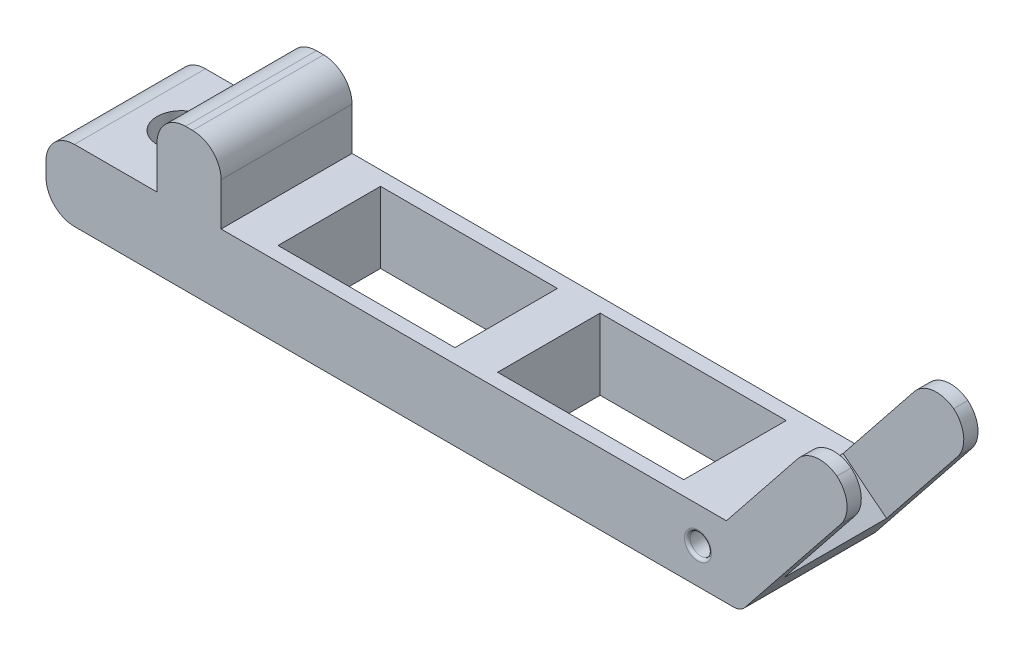
SolidWorks part; units mm, degrees
ref_plane "Front Plane" through (0, 0, 0) normal (0, 0, 1) x (1, 0, 0)
ref_plane "Top Plane" through (0, 0, 0) normal (0, 1, 0) x (1, 0, 0)
ref_plane "Right Plane" through (0, 0, 0) normal (1, 0, 0) x (0, 0, -1)
sketch "Szkic1" plane through (0, 0, 0) normal (0, 0, 1) x (1, 0, 0)
  line L6 (-27646.5587, -28.9023) -> (-27646.5587, -33.9023)
  line L7 (-27646.5587, -33.9023) -> (-27597.7587, -33.9023)
  line L8 (-27597.7587, -33.9023) -> (-27589.4735, -23.5176)
  line L9 (-27589.4735, -23.5176) -> (-27592.5221, -21.0854)
  line L10 (-27592.5221, -21.0854) -> (-27598.7587, -28.9023)
  line L11 (-27598.7587, -28.9023) -> (-27634.2587, -28.9023)
  line L12 (-27638.7587, -28.9023) -> (-27638.7587, -23.9023)
  line L13 (-27638.7587, -23.9023) -> (-27634.2587, -23.9023)
  line L14 (-27634.2587, -23.9023) -> (-27634.2587, -28.9023)
  line L15 (-27638.7587, -28.9023) -> (-27646.5587, -28.9023)
  line L16 (-27600.7587, -28.9023) -> (-27600.7587, -33.9023) construction
  circle A0 centre (-27600.7587, -31.4023) radius 0.75
  point P12 (-27600.7587, -31.4023)
  dimension "D9" = 1.5
  dimension "D1" = 3.9
  dimension "D2" = 47.8
  dimension "D3" = 10
  dimension "D4" = 5
  dimension "D5" = 48.8
  dimension "D6" = 4.5
  dimension "D7" = 5
  dimension "D8" = 7.8
  dimension "D10" = 2
extrude "Dodanie-wyciągnięcie1" add sketch "Szkic1" along normal blind 9.2
fillet "Zaokrąglenie1" radius 2 4 edges at (-27646.5587, -33.9023, 4.6) (-27634.2587, -23.9023, 4.6) (-27638.7587, -23.9023, 4.6) (-27646.5587, -28.9023, 4.6)
fillet "Zaokrąglenie3" radius 1 1 edges at (-27597.7587, -33.9023, 4.6)
ref_plane "Płaszczyzna1" through (0, -28.9023, 0) normal (0, 1, 0) x (1, 0, 0)
sketch "Szkic2" plane through (0, -28.9023, 0) normal (0, 1, 0) x (1, 0, 0)
  line L0 (-27641.6587, 0) -> (-27641.6587, -9.2) construction
  line L1 (-27638.7587, 0) -> (-27644.5587, 0) construction
  line L2 (-27638.7587, -9.2) -> (-27644.5587, -9.2) construction
  circle A0 centre (-27641.6587, -4.6) radius 1.7
  point P6 (-27641.6587, -4.6)
  dimension "D1" = 3.4
extrude "Wytnij-wyciągnięcie1" cut sketch "Szkic2" against normal through all
ref_plane "Płaszczyzna2" through (0, -28.9023, 0) normal (0, 1, 0) x (1, 0, 0)
sketch "Szkic3" plane through (0, -28.9023, 0) normal (0, 1, 0) x (1, 0, 0)
  line L0 (-27634.2587, -4.6) -> (-27598.7587, -4.6) construction
  line L1 (-27634.2587, -9.2) -> (-27634.2587, 0) construction
  line L2 (-27598.7587, -9.2) -> (-27598.7587, 0) construction
  line L3 (-27598.7587, -9.2) -> (-27634.2587, -9.2) construction
  line L4 (-27602.7587, -8.2) -> (-27615.8325, -8.2)
  line L5 (-27602.7587, -8.2) -> (-27602.7587, -1)
  line L6 (-27602.7587, -1) -> (-27615.8325, -1)
  line L7 (-27615.8325, -8.2) -> (-27615.8325, -1)
  line L8 (-27602.7587, -8.2) -> (-27615.8325, -1) construction
  line L9 (-27602.7587, -1) -> (-27615.8325, -8.2) construction
  line L10 (-27631.2587, -1) -> (-27618.8325, -1)
  line L11 (-27631.2587, -1) -> (-27631.2587, -8.2)
  line L12 (-27631.2587, -8.2) -> (-27618.8325, -8.2)
  line L13 (-27618.8325, -1) -> (-27618.8325, -8.2)
  line L14 (-27631.2587, -1) -> (-27618.8325, -8.2) construction
  line L15 (-27631.2587, -8.2) -> (-27618.8325, -1) construction
  point P6 (-27609.2956, -4.6)
  point P11 (-27625.0456, -4.6)
  dimension "D1" = 3
  dimension "D2" = 4
  dimension "D3" = 3
  dimension "D4" = 1
extrude "Wytnij-wyciągnięcie2" cut sketch "Szkic3" against normal through all
ref_plane "Płaszczyzna3" through (-16850.0467, 13443.5022, 0) normal (-0.7817, 0.6237, 0) x (0, 0, 1)
sketch "Szkic4" plane through (-16850.0467, 13443.5022, 0) normal (-0.7817, 0.6237, 0) x (0, 0, 1)
  line L0 (9.2, -17234.8628) -> (0, -17234.8628) construction
  line L1 (1, -17234.8628) -> (8.2, -17234.8628)
  line L2 (1, -17234.8628) -> (1, -17222.0924)
  line L3 (1, -17222.0924) -> (8.2, -17222.0924)
  line L4 (8.2, -17234.8628) -> (8.2, -17222.0924)
  line L5 (0, -17224.8628) -> (0, -17234.8628) construction
  dimension "D1" = 7.2
  dimension "D2" = 1
extrude "Wytnij-wyciągnięcie3" cut sketch "Szkic4" against normal through all
ref_plane "Płaszczyzna4" through (0, 0, 1) normal (0, 0, 1) x (1, 0, 0)
sketch "Szkic5" plane through (0, 0, 1) normal (0, 0, 1) x (1, 0, 0)
  line L0 (-27590.9978, -22.3015) -> (-27597.2344, -30.1185) construction
  line L1 (-27592.5221, -21.0854) -> (-27589.4735, -23.5176) construction
  line L2 (-27595.7101, -31.3346) -> (-27598.7587, -28.9023) construction
  circle A0 centre (-27592.3166, -23.9544) radius 0.5
  dimension "D1" = 1
extrude "Dodanie-wyciągnięcie2" [suppressed] add sketch "Szkic5" along normal up to next
fillet "Zaokrąglenie4" radius 2 4 edges at (-27589.4735, -23.5176, 0.5) (-27592.5221, -21.0854, 0.5) (-27589.4735, -23.5176, 8.7) (-27592.5221, -21.0854, 8.7)
fillet "Zaokrąglenie5" radius 1 1 edges at (-27643.3587, -33.9023, 4.6)
ref_axis "Oś1" through (-27641.6587, -32.9023, 4.6) along (0, 1, 0)
ref_point "Punkt1"
ref_point "Punkt2"
ref_plane "Płaszczyzna5" through (0, 0, 4.6) normal (0, 0, -1) x (-1, 0, 0)
sketch "Szkic7" plane through (0, 0, 4.6) normal (0, 0, -1) x (-1, 0, 0)
  line L0 (27638.5808, -32.7023) -> (27642.151, -32.7023) construction
  line L2 (27641.6587, -32.9023) -> (27641.6587, -28.9023) construction
  circle A0 centre (27639.9587, -32.7023) radius 0.15
  point P2 (27639.9587, -32.7023)
  point P4 (27641.6587, -28.9023)
  dimension "D3" = 0.3
  dimension "D1" = 3.8
  dimension "D2" = 1.7
revolve "Wycięcie-obrót2" cut sketch "Szkic7" angle 360 about axis through (-27641.6587, -32.9023, 4.6) along (0, 1, 0)
fillet "Zaokrąglenie6" radius 0.1 2 edges at (-27641.6587, -32.5523, 2.9) (-27641.6587, -32.8523, 6.3)
fillet "Zaokrąglenie7" radius 0.2 2 edges at (-27600.0087, -31.4023, 9.2) (-27600.0087, -31.4023, 0)
ref_plane "Płaszczyzna Dolnia" through (0, -33.9023, 0) normal (0, -1, 0) x (-1, 0, 0)
